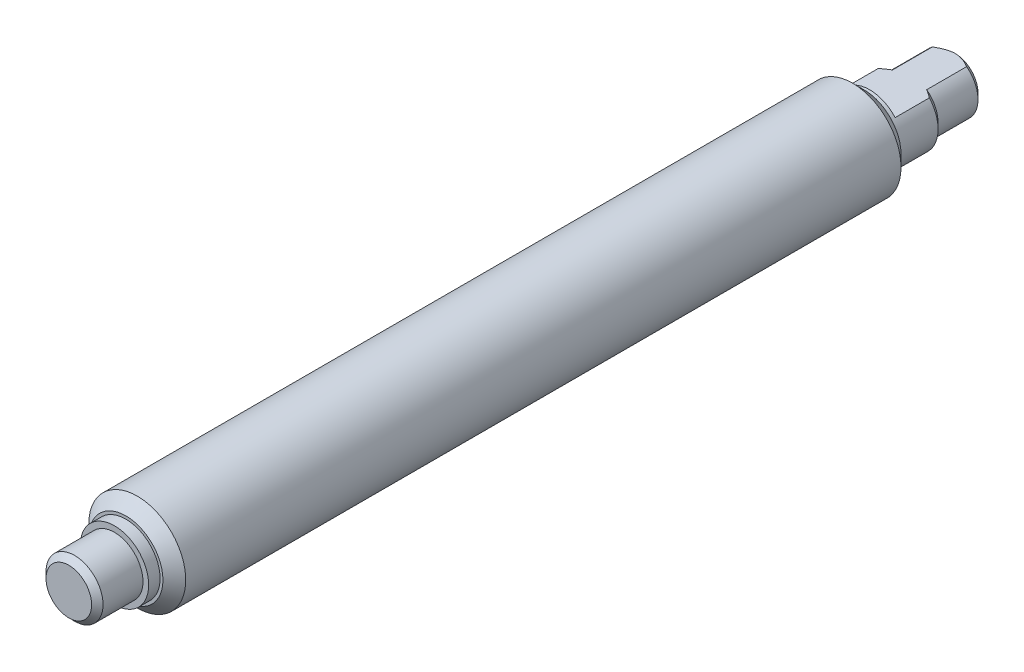
SolidWorks part; units mm, degrees
material "2A12"
ref_plane "前视基准面" through (0, 0, 0) normal (0, 0, 1) x (1, 0, 0)
ref_plane "上视基准面" through (0, 0, 0) normal (0, 1, 0) x (1, 0, 0)
ref_plane "右视基准面" through (0, 0, 0) normal (1, 0, 0) x (0, 0, -1)
sketch "草图1" plane through (0, 0, 0) normal (0, 0, 1) x (1, 0, 0)
  circle A0 centre (0, 0) radius 4.25
  dimension "D1" = 8.5
extrude "拉伸1" add sketch "草图1" along normal mid plane 64.7
sketch "草图2" plane through (0, 0, 32.35) normal (0, 0, 1) x (1, 0, 0)
  circle A0 centre (0, 0) radius 3
  dimension "D1" = 6
extrude "拉伸2" add sketch "草图2" along normal blind 1
sketch "草图3" plane through (0, 0, 33.35) normal (0, 0, 1) x (1, 0, 0)
  circle A0 centre (0, 0) radius 2.5
  dimension "D1" = 5
extrude "拉伸3" add sketch "草图3" along normal blind 4
sketch "草图4" plane through (0, 0, -32.35) normal (0, 0, -1) x (-1, 0, 0)
  circle A0 centre (0, 0) radius 3
  dimension "D1" = 6
extrude "拉伸4" add sketch "草图4" along normal blind 4
sketch "草图5" plane through (0, 0, -36.35) normal (0, 0, -1) x (-1, 0, 0)
  circle A0 centre (0, 0) radius 2.5
  dimension "D1" = 5
extrude "拉伸5" add sketch "草图5" along normal blind 4
chamfer "倒角1" distance 0.5 angle 45 2 edges at (-2.5, 0, -40.35) (2.5, 0, 37.35)
chamfer "倒角2" distance 0.5 angle 45 1 edges at (-3, 0, -36.35)
sketch "草图6" plane through (0, 0, -40.35) normal (0, 0, -1) x (-1, 0, 0)
  line L0 (0, 0) -> (0, 2) construction
  line L1 (-3, 5) -> (3, 5)
  line L2 (-3, 5) -> (-3, 2)
  line L3 (-3, 2) -> (3, 2)
  line L4 (3, 5) -> (3, 2)
  dimension "D1" = 2
  dimension "D2" = 3
  dimension "D3" = 6
extrude "拉伸6" cut sketch "草图6" against normal blind 7.5
chamfer "Chamfer1" distance 1 angle 45 2 edges at (4.25, 0, -32.35) (4.25, 0, 32.35)
